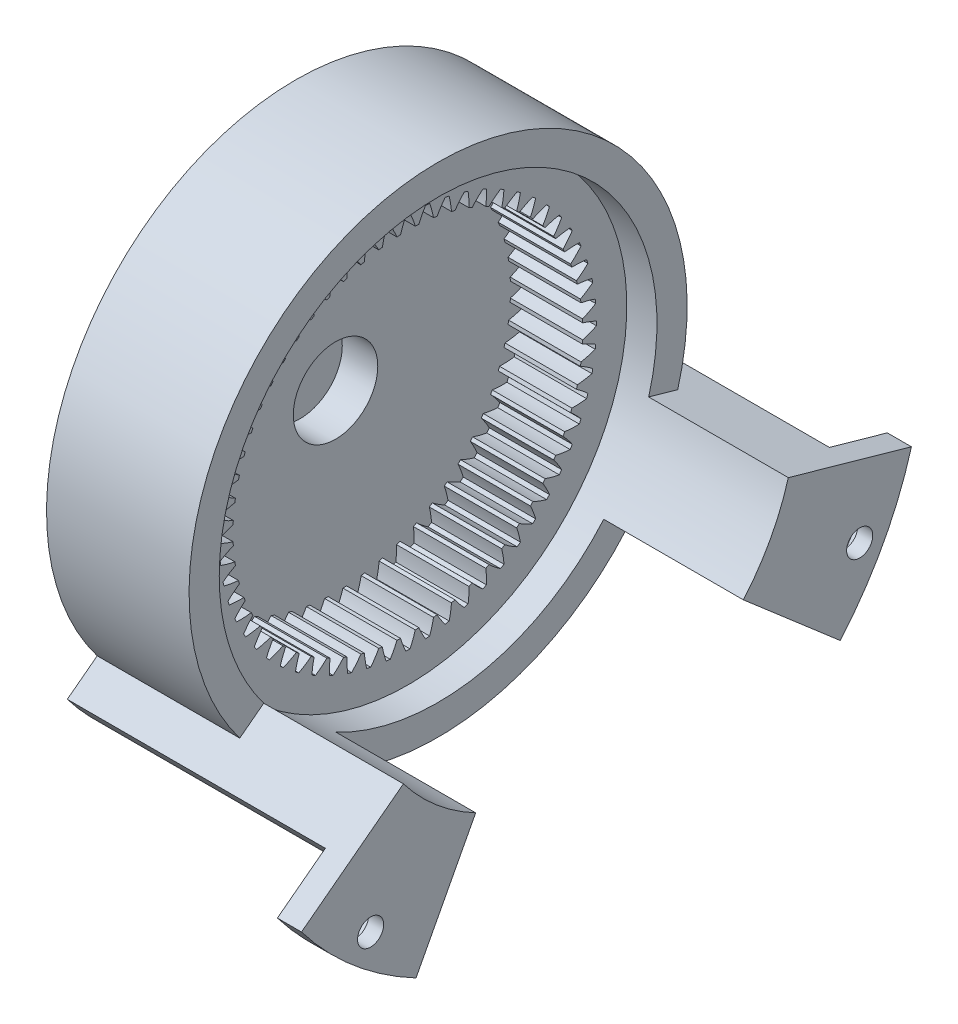
SolidWorks part; units mm, degrees
ref_plane "Plane1" through (0, 0, 0) normal (0, 0, 1) x (1, 0, 0)
ref_plane "Plane2" through (0, 0, 0) normal (0, 1, 0) x (1, 0, 0)
ref_plane "Plane3" through (0, 0, 0) normal (1, 0, 0) x (0, 0, -1)
sketch "HoldingSke" plane through (0, 0, 0) normal (0, 1, 0) x (1, 0, 0)
  line L0 (0, 0) -> (0.5, -0.866)
  line L1 (-15, 0) -> (100, 0) construction
  line L2 (0, 0) -> (-2.1039, 2.3779)
  line L3 (0, 0) -> (-11.863, 4.5341)
  line L4 (0, 0) -> (4.318, 7.479)
  line L5 (0, 0) -> (-23.7986, -8.8762)
  line L6 (0, 0) -> (-10.5278, -7.1032)
  line L7 (-2.1039, 2.3779) -> (3.3635, 27.1825)
  line L8 (-76.2, 3.3779) -> (-54.61, 3.3779)
  line L9 (-71.009, 38.7566) -> (-53.1078, 45.2721)
  line L10 (-76.2, 71.12) -> (104.1128, 71.12)
  line L11 (0, 0) -> (-12, 0)
  line L12 (-76.2, 101.6) -> (-76.162, 101.6)
  line L13 (24.9733, 27.94) -> (52.9518, 28.4284)
  line L14 (24.9733, 27.94) -> (24.9743, 27.94)
  line L15 (24.9733, 27.94) -> (100.4006, 29.5858)
  circle A0 centre (0, 0) radius 12.5
  circle A1 centre (0, 0) radius 12.7
  circle A2 centre (0, 0) radius 12.7
  dimension "MHD" = 25.4
  dimension "Hub_dia" = 25.4
  dimension "Diameter" = 25
  dimension "Num_teeth" = 60
  dimension "Pitch" = 1
  dimension "Overall_len" = 25.4
  dimension "Show_teeth" = 60
  dimension "Thickness" = 12.7
  dimension "OAL" = 25.4001
  dimension "T_dim" = 21.59
  dimension "Ap" = 20
  dimension "H" = 19.05
  dimension "Pitch_radius" = 180.3128
  dimension "Width" = 12
  dimension "Backlash" = 0.038
  dimension "Addendum_fac" = 1
  dimension "Dedendum_fac" = 1.25
  dimension "Clearance_fac" = 0.25
  dimension "Dedendum_add" = 0.001
  dimension "Module" = 1
sketch "BasProSke" plane through (0, 0, 0) normal (0, 1, 0) x (1, 0, 0)
  line L0 (-10, 0) -> (60, 0) construction
  line L1 (0, 29) -> (0, 31.2764)
  line L2 (0, 29) -> (12, 29)
  line L3 (12, 29) -> (12, 31.2764)
  line L4 (12, 31.2764) -> (0, 31.2764)
  dimension "Thickness" = 12
  dimension "Diameter" = 62.5528
  dimension "Inside_diameter" = 58
revolve "Base-Revolve" add sketch "BasProSke" angle 360 about L0
sketch "TooCutSke" plane through (0, 0, 0) normal (1, 0, 0) x (0, 0, -1)
  line L3 (0.8803, 29.9871) -> (0.8803, 53.6633) construction
  line L4 (0, 0) -> (0, 59.563) construction
  line L5 (0, 0) -> (-3.576, 68.2339) construction
  line L6 (-13.1633, 24.7167) -> (36.4631, 27.3175) construction
  circle A0 centre (0, 0) radius 30 construction
  circle A1 centre (0, 0) radius 31.251 construction
  circle A2 centre (0, 0) radius 25.3717 construction
  circle A3 centre (0, 0) radius 28.9746 construction
  arc A4 (1.2274, 28.9486) -> (0.3395, 31.2492) centre (-13.1633, 24.7167) ccw
  arc A5 (1.2274, 28.9486) -> (-1.2274, 28.9486) centre (0, 0) ccw
  arc A6 (0.3395, 31.2492) -> (-0.3395, 31.2492) centre (0, 0) ccw
  arc A7 (-0.3395, 31.2492) -> (-1.2274, 28.9486) centre (13.1633, 24.7167) ccw
  dimension "Pitch_dia" = 60
  dimension "Base_dia" = 50.7434
  dimension "Root_dia" = 62.502
  dimension "Overcut_dia" = 57.9492
  dimension "Flank_rad" = 15
  dimension "Half_ang" = 3
  dimension "Half_CT" = 0.8803
extrude "ToothCut" cut sketch "TooCutSke" along normal through all
fillet "Breaks" [suppressed] radius 0.1
fillet "RootFillets" [suppressed] radius 0.251
pattern_circular "TeethCuts" count 60 every 6 about axis through (-10, 0, 0) along (1, 0, 0) of "RootFillets", "Breaks", "ToothCut"
scale "Scale1" scale about centroid uniform scaling yes scale factor 2
sketch "Sketch1" plane through (18, 0, 0) normal (1, 0, 0) x (0, 0, -1)
  circle A0 centre (0, 0) radius 62.5528
extrude "Extrude-Thin1" add sketch "Sketch1" against normal blind 35 separate body thin thin type one direction wall 10
sketch "Sketch2" plane through (-6, 0, 0) normal (-1, 0, 0) x (0, 0, 1)
  circle A0 centre (0, 0) radius 62.5528
extrude "Boss-Extrude1" add sketch "Sketch2" along normal blind 11
sketch "Sketch3" plane through (-6, 0, 0) normal (1, 0, 0) x (0, 0, -1)
  circle A0 centre (0, 0) radius 14
  dimension "D1" = 28
extrude "Cut-Extrude1" cut sketch "Sketch3" against normal through all
sketch "Sketch6" plane through (-17, 0, 0) normal (-1, 0, 0) x (0, 0, 1)
  circle A0 centre (0, 0) radius 82.5528
  circle A1 centre (0, 0) radius 72.5528
  dimension "D1" = 10
extrude "Boss-Extrude2" add sketch "Sketch6" against normal blind 45 separate body
sketch "Sketch7" plane through (28, 0, 0) normal (1, 0, 0) x (0, 0, -1)
  line L0 (0, 0) -> (56.1752, -14.4344) construction
  line L1 (0, 0) -> (71.903, -62.0883) construction
  line L3 (79.4296, -22.4922) -> (91.4059, -25.8836) construction
  line L6 (0, 0) -> (-44.3, -84.0387) construction
  line L7 (0, 0) -> (-75.6658, -57.443) construction
  line L8 (-44.3, -84.0387) -> (-38.4957, -73.0277)
  line L9 (-75.6658, -57.443) -> (-65.7518, -49.9166)
  line L10 (71.903, -62.0883) -> (62.4821, -53.9533)
  line L11 (91.4059, -25.8836) -> (79.4296, -22.4922)
  circle A0 centre (0, 0) radius 82.5528 construction
  arc A5 (71.903, -62.0883) -> (91.4059, -25.8836) centre (0, 0) ccw
  arc A6 (62.4821, -53.9533) -> (79.4296, -22.4922) centre (0, 0) ccw
  arc A7 (-65.7518, -49.9166) -> (-38.4957, -73.0277) centre (0, 0) ccw
  arc A8 (-75.6658, -57.443) -> (-44.3, -84.0387) centre (0, 0) ccw
  dimension "D2" = 25
  dimension "D1" = 1.4
  dimension "D3" = 25
  dimension "D4" = 101.985
extrude "Boss-Extrude9" add sketch "Sketch7" against normal through all
sketch "Sketch20" plane through (28, 0, 0) normal (1, 0, 0) x (0, 0, -1)
  line L0 (91.4059, -25.8836) -> (110.6213, -31.3248)
  line L1 (71.903, -62.0883) -> (87.0185, -75.1405)
  line L2 (-44.3, -84.0387) -> (-53.6128, -101.7054)
  line L3 (-75.6658, -57.443) -> (-91.5722, -69.5186)
  line L4 (62.4821, -53.9533) -> (71.903, -62.0883) construction
  arc A0 (71.903, -62.0883) -> (91.4059, -25.8836) centre (0, 0) ccw
  arc A1 (87.0185, -75.1405) -> (110.6213, -31.3248) centre (0, 0) ccw
  arc A2 (-75.6658, -57.443) -> (-44.3, -84.0387) centre (0, 0) ccw
  arc A3 (-91.5722, -69.5186) -> (-53.6128, -101.7054) centre (0, 0) ccw
sketch "Sketch22" plane through (28, 0, 0) normal (1, 0, 0) x (0, 0, -1)
  line L0 (0, 0) -> (93.4685, -50.3499)
  line L1 (0, 0) -> (-68.6614, -80.9758)
  line L2 (91.4059, -25.8836) -> (79.4296, -22.4922) construction
  line L3 (-44.3, -84.0387) -> (-38.4957, -73.0277) construction
  dimension "D1" = 106.1672
  dimension "D2" = 106.1672
  dimension "D3" = 12.5
  dimension "D4" = 12.5
sketch "Sketch25" plane through (28, 0, 0) normal (1, 0, 0) x (0, 0, -1)
  line L0 (62.4821, -53.9533) -> (71.903, -62.0883)
  line L1 (91.4059, -25.8836) -> (79.4296, -22.4922)
  line L2 (-38.4957, -73.0277) -> (-44.3, -84.0387)
  line L3 (-65.7518, -49.9166) -> (-75.6658, -57.443)
  arc A0 (71.903, -62.0883) -> (91.4059, -25.8836) centre (0, 0) ccw
  arc A1 (62.4821, -53.9533) -> (79.4296, -22.4922) centre (0, 0) ccw
  arc A2 (-65.7518, -49.9166) -> (-38.4957, -73.0277) centre (0, 0) ccw
  arc A3 (-75.6658, -57.443) -> (-44.3, -84.0387) centre (0, 0) ccw
extrude "Boss-Extrude11" add sketch "Sketch25" along normal blind 46.2863
sketch "Sketch26" plane through (74.2863, 0, 0) normal (1, 0, 0) x (0, 0, -1)
  line L0 (110.6213, -31.3248) -> (91.4059, -25.8836)
  line L1 (87.0185, -75.1405) -> (71.903, -62.0883)
  line L2 (-53.6128, -101.7054) -> (-44.3, -84.0387)
  line L3 (-91.5722, -69.5186) -> (-75.6658, -57.443)
  arc A0 (87.0185, -75.1405) -> (110.6213, -31.3248) centre (0, 0) ccw
  arc A1 (71.903, -62.0883) -> (91.4059, -25.8836) centre (0, 0) ccw
  arc A2 (-75.6658, -57.443) -> (-44.3, -84.0387) centre (0, 0) ccw
  arc A3 (-91.5722, -69.5186) -> (-53.6128, -101.7054) centre (0, 0) ccw
extrude "Boss-Extrude12" add sketch "Sketch26" against normal blind 8
hole_wizard "Ø1.0mm Dowel Hole6" positions "3DSketch6" profile "Sketch28" hole size "Ø1.0" standard "ANSI Metric" end condition through all
sketch3d "3DSketch6"
  point P0 (28, -80.9758, 68.6614)
  point P4 (28, -50.3499, -93.4685)
sketch "Sketch28" plane through (28, -80.9758, 68.6614) normal (0, 1, 0) x (0, 0, 1)
  line L0 (0, 0) -> (0, 46.2863)
  line L1 (0, 46.2863) -> (4.33, 46.2863)
  line L2 (4.33, 46.2863) -> (4.33, 0)
  line L5 (4.33, 0) -> (0, 0)
  line L11 (0, -6.35) -> (0, 107.95) construction
  dimension "Thru Hole Dia." = 8.66
  dimension "Thru Hole Depth" = 46.2863
sketch "Sketch29" plane through (66.2863, 0, 0) normal (-1, 0, 0) x (0, 0, 1)
  line L1 (66.2029, -88.5887) -> (74.0251, -86.9114)
  line L2 (74.0251, -86.9114) -> (76.4836, -79.2986)
  line L3 (76.4836, -79.2986) -> (71.1199, -73.363)
  line L4 (71.1199, -73.363) -> (63.2977, -75.0403)
  line L5 (63.2977, -75.0403) -> (60.8392, -82.6531)
  line L6 (60.8392, -82.6531) -> (66.2029, -88.5887)
  line L7 (-89.1559, -57.088) -> (-85.4769, -49.9841)
  line L8 (-85.4769, -49.9841) -> (-89.7895, -43.2461)
  line L9 (-89.7895, -43.2461) -> (-97.7811, -43.6119)
  line L10 (-97.7811, -43.6119) -> (-101.4601, -50.7158)
  line L11 (-101.4601, -50.7158) -> (-97.1475, -57.4538)
  line L12 (-97.1475, -57.4538) -> (-89.1559, -57.088)
  circle A0 centre (68.6614, -80.9758) radius 6.9282 construction
  circle A1 centre (-93.4685, -50.3499) radius 6.9282 construction
  dimension "D1" = 8
  dimension "D2" = 8
extrude "Cut-Extrude7" cut sketch "Sketch29" against normal blind 3
sketch "Sketch30" plane through (28, 0, 0) normal (1, 0, 0) x (0, 0, -1)
  line L0 (62.4821, -53.9533) -> (54.9133, -47.4177)
  line L1 (79.4296, -22.4922) -> (69.8079, -19.7676)
  line L2 (-38.4957, -73.0277) -> (-33.8325, -64.1815)
  line L3 (-65.7518, -49.9166) -> (-57.787, -43.87)
  arc A0 (62.4821, -53.9533) -> (79.4296, -22.4922) centre (0, 0) ccw
  arc A1 (54.9133, -47.4177) -> (69.8079, -19.7676) centre (0, 0) ccw
  arc A2 (-57.787, -43.87) -> (-33.8325, -64.1815) centre (0, 0) ccw
  arc A3 (-65.7518, -49.9166) -> (-38.4957, -73.0277) centre (0, 0) ccw
extrude "Boss-Extrude13" add sketch "Sketch30" along normal blind 46.2863
scale "Scale5" bodies to scale 143 107 scale about origin uniform scaling yes scale factor 0.666667
sketch "Sketch31" plane through (-11.3333, 0, 0) normal (-1, 0, 0) x (0, 0, 1)
  circle A0 centre (0, 0) radius 55.0352
extrude "Boss-Extrude14" add sketch "Sketch31" along normal blind 1.5
sketch "Sketch32" plane through (-11.3333, 0, 0) normal (1, 0, 0) x (0, 0, -1)
  circle A0 centre (0, 0) radius 9.3333
extrude "Cut-Extrude8" cut sketch "Sketch32" against normal blind 0.5045
sketch "Sketch33" plane through (-12.8333, 0, 0) normal (-1, 0, 0) x (0, 0, 1)
  line L0 (50.4438, -38.2953) -> (43.8345, -33.2777)
  line L1 (43.8345, -33.2777) -> (50.4438, -38.2953) construction
  line L2 (29.5334, -56.0258) -> (25.6638, -48.6851)
  line L3 (29.5334, -56.0258) -> (25.6638, -48.6851) construction
  line L4 (-47.9354, -41.3922) -> (-41.6547, -35.9689)
  line L5 (-60.9373, -17.2557) -> (-52.9531, -14.9948)
  arc A0 (-60.9373, -17.2557) -> (-47.9354, -41.3922) centre (0, 0) ccw
  arc A1 (-52.9531, -14.9948) -> (-41.6547, -35.9689) centre (0, 0) ccw
  circle A2 centre (0, 0) radius 55.0352 construction
  arc A3 (29.5334, -56.0258) -> (50.4438, -38.2953) centre (0, 0) ccw construction
  arc A4 (25.6638, -48.6851) -> (43.8345, -33.2777) centre (0, 0) ccw
  arc A5 (29.5334, -56.0258) -> (50.4438, -38.2953) centre (0, 0) ccw
extrude "Boss-Extrude15" add sketch "Sketch33" against normal blind 1.5
equation "' \"Module@HoldingSke\" = 6.35"
equation "' \"Num_teeth@HoldingSke\" = 24"
equation "' \"Ap@HoldingSke\" =  14.5"
equation "' \"Ap@HoldingSke\" = 14.5"
equation "' \"Width@HoldingSke\" = 12"
equation "' \"Diameter@HoldingSke\" = 8 * 25.4"
equation "' \"Show_teeth@HoldingSke\" = 100"
equation "' \"Backlash@HoldingSke\" = 0.009 * 25.4"
equation "' \"Addendum_fac@HoldingSke\" = 1.0"
equation "' \"Dedendum_fac@HoldingSke\" = 1.25"
equation "' \"Dedendum_add@HoldingSke\" = 0.00005 * 25.4"
equation "' \"Clearance_fac@HoldingSke\" = 0.25"
equation "\"Pitch@HoldingSke\" = 1 / \"Module@HoldingSke\" "
equation "\"Overcut_dia@TooCutSke\" = (\"Num_teeth@HoldingSke\" - 2 * \"Addendum_fac@HoldingSke\") / \"Pitch@HoldingSke\" - 0.002 * 25.4"
equation "\"Pitch_dia@TooCutSke\" = \"Num_teeth@HoldingSke\" / \"Pitch@HoldingSke\""
equation "\"Base_dia@TooCutSke\" = \"Num_teeth@HoldingSke\" / \"Pitch@HoldingSke\" * cos((\"Ap@HoldingSke\"  * 3.14159265 / 180)) * 0.90"
equation "\"Root_dia@TooCutSke\" = \"Num_teeth@HoldingSke\"  / \"Pitch@HoldingSke\" + 2 *  \"Dedendum_fac@HoldingSke\"/ \"Pitch@HoldingSke\" + \"Dedendum_add@HoldingSke\" * 2"
equation "\"Half_ang@TooCutSke\" = 180 / \"Num_teeth@HoldingSke\""
equation "\"Half_CT@TooCutSke\" = \"Num_teeth@HoldingSke\" / \"Pitch@HoldingSke\" * sin((3.14159265 / 2 / \"Num_teeth@HoldingSke\")) / 2 + 10 * \"Backlash@HoldingSke\" / 4"
equation "\"Flank_rad@TooCutSke\" = \"Num_teeth@HoldingSke\" / \"Pitch@HoldingSke\" / 4"
equation "\"Radius@RootFillets\"= \"Clearance_fac@HoldingSke\" / \"Pitch@HoldingSke\" + \"Dedendum_add@HoldingSke\""
equation "\"Break_rad@Breaks\" = 0.02 / \"Pitch@HoldingSke\" * 5"
equation "\"Num_teeth@TeethCuts\" = int( \"Show_teeth@HoldingSke\" ) + 1"
equation "\"Num_teeth@TeethCuts\" = ((sgn( \"Num_teeth@TeethCuts\" - \"Num_teeth@HoldingSke\" )-1)*( \"Num_teeth@TeethCuts\" - \"Num_teeth@HoldingSke\" ))/-2+ \"Num_teeth@HoldingSke\""
equation "\"Num_teeth@TeethCuts\" = ((sgn( \"Num_teeth@TeethCuts\" - 2.0)+1)*( \"Num_teeth@TeethCuts\" - 2.0))/2 +2.0"
equation "\"Angle@TeethCuts\" = 360.0 / \"Num_teeth@HoldingSke\""
equation "\"Diameter@BasProSke\" = \"Num_teeth@HoldingSke\"  / \"Pitch@HoldingSke\" + 2 *  \"Dedendum_fac@HoldingSke\"/ \"Pitch@HoldingSke\" + \"Dedendum_add@HoldingSke\" * 2 + 0.002 * 25.4"
equation "\"Diameter@BasProSke\" = ((sgn( \"Diameter@BasProSke\"  - \"Diameter@HoldingSke\" )+1)*( \"Diameter@BasProSke\"  - \"Diameter@HoldingSke\" ))/2 + \"Diameter@HoldingSke\""
equation "\"Inside_diameter@BasProSke\" =  (\"Num_teeth@HoldingSke\" - 2 * \"Addendum_fac@HoldingSke\") / \"Pitch@HoldingSke\" "
equation "\"Thickness@BasProSke\"  = \"Width@HoldingSke\""
